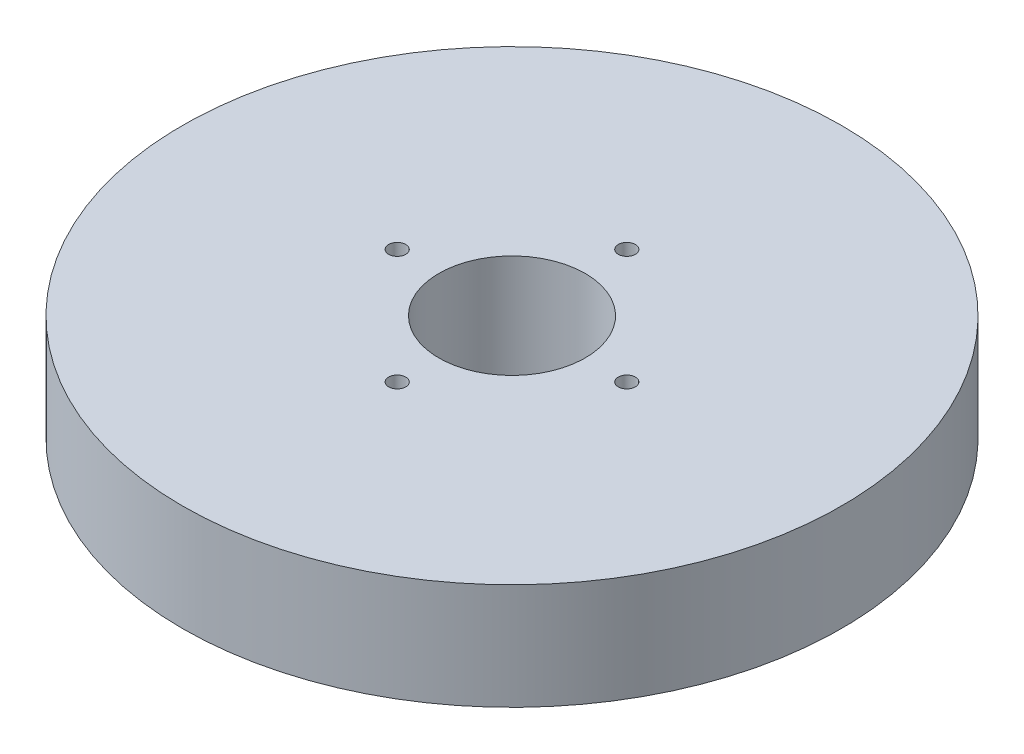
SolidWorks part; units mm, degrees
ref_plane "Front Plane" through (0, 0, 0) normal (0, 0, 1) x (1, 0, 0)
ref_plane "Top Plane" through (0, 0, 0) normal (0, 1, 0) x (1, 0, 0)
ref_plane "Right Plane" through (0, 0, 0) normal (1, 0, 0) x (0, 0, -1)
sketch "Sketch1" plane through (0, 0, 0) normal (0, 1, 0) x (1, 0, 0)
  circle A0 centre (0, 0) radius 90
  dimension "FLANGE_OD" = 180
extrude "Boss-Extrude1" add sketch "Sketch1" along normal blind 29
sketch "Sketch2" plane through (0, 0, 0) normal (0, 1, 0) x (1, 0, 0)
  circle A0 centre (0, 0) radius 20
  dimension "BORE_D" = 40
extrude "Cut-Extrude1" cut sketch "Sketch2" along normal through all
sketch "Sketch3" plane through (0, 29, 0) normal (0, 1, 0) x (1, 0, 0)
  circle A0 centre (0, 0) radius 31.3524 construction
  circle A1 centre (-31.3524, 0) radius 2.3387
  dimension "BOLT_D" = 4.6774
  dimension "BOLT_PCD" = 62.7048
extrude "Cut-Extrude2" cut sketch "Sketch3" against normal blind 19.3301
pattern_circular "CirPattern1" count 4 over 360 about axis through (0, 0, 0) along (0, 1, 0) of "Cut-Extrude2"
